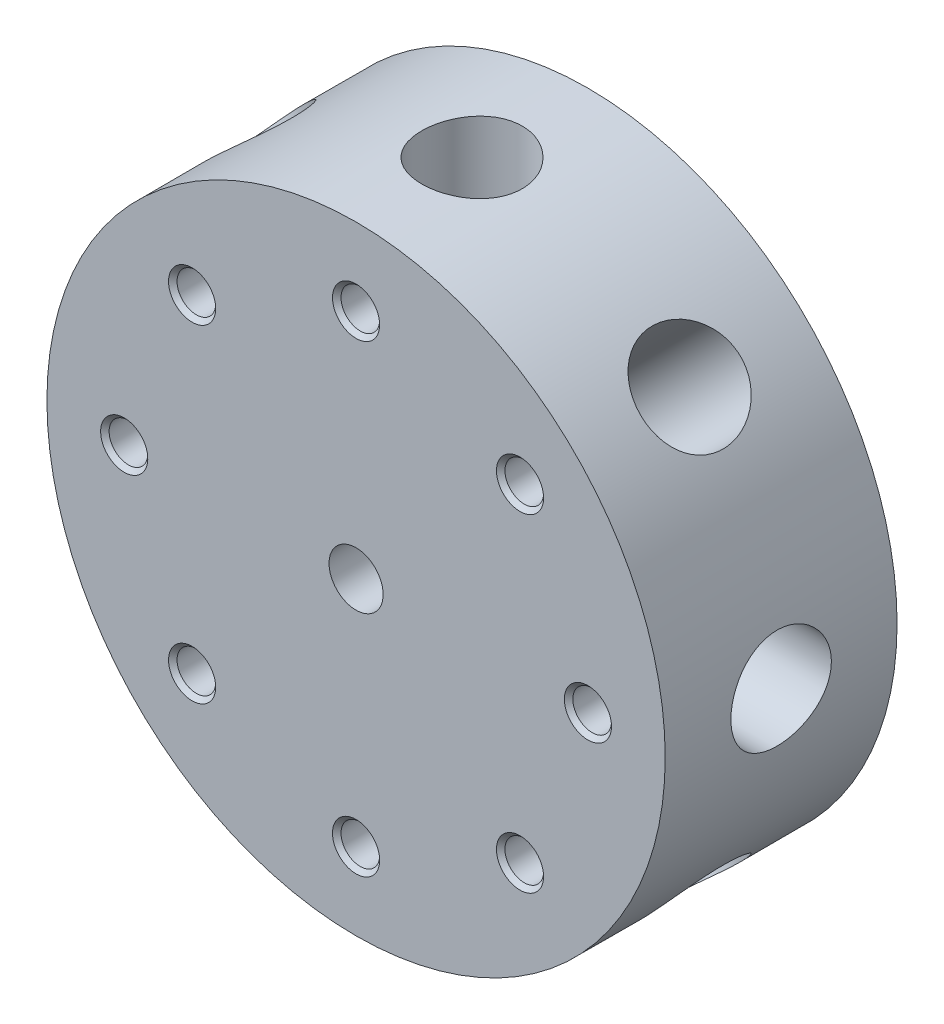
SolidWorks part; units mm, degrees
material "Nylon 101"
ref_plane "Front Plane" through (0, 0, 0) normal (0, 0, 1) x (1, 0, 0)
ref_plane "Top Plane" through (0, 0, 0) normal (0, 1, 0) x (1, 0, 0)
ref_plane "Right Plane" through (0, 0, 0) normal (1, 0, 0) x (0, 0, -1)
sketch "Sketch1" plane through (0, 0, 0) normal (0, 0, 1) x (1, 0, 0)
  circle A0 centre (0, 0) radius 40
  dimension "D1" = 80
extrude "Blank" add sketch "Sketch1" along normal mid plane 30
ref_plane "Plane1" through (0, 40, 0) normal (0, 1, 0) x (1, 0, 0)
hole_wizard "Ø12.0 stem hole" positions "Sketch7" profile "Sketch6" hole size "Ø12.0" standard "ANSI Metric"
sketch "Sketch7" plane through (0, 40, 0) normal (0, 1, 0) x (1, 0, 0)
  point P0 (0, 0)
sketch "Sketch6" plane through (0, 40, 0) normal (1, 0, 0) x (0, 0, 1)
  line L0 (0, 0) -> (0, 25.9056)
  line L1 (0, 25.9056) -> (6.5, 22)
  line L2 (6.5, 22) -> (6.5, 0)
  line L5 (6.5, 0) -> (0, 0)
  line L10 (0, 25.9056) -> (-6.5, 22) construction
  line L11 (0, -6.35) -> (0, 107.95) construction
  dimension "Hole Dia." = 13
  dimension "Hole Depth" = 22
  dimension "Drill Angle" = 118
hole_wizard "M6x1.0 Tapped Hole for grub screw" positions "Sketch4" profile "Sketch3" tap size "M6x1.0" standard "ANSI Metric" end condition up to next
sketch "Sketch4" plane through (0, 0, 15) normal (0, 0, 1) x (1, 0, 0)
  line L0 (0, 0) -> (0, 40) construction
  line L1 (16.5, 40) -> (-16.5, 40) construction
  circle A0 centre (0, 0) radius 40 construction
  point P0 (0, 30)
  dimension "D1" = 30
sketch "Sketch3" plane through (0, 30, 15) normal (1, 0, 0) x (0, -1, 0)
  line L0 (0, 0) -> (0, 8.5)
  line L1 (0, 8.5) -> (2.5, 8.5)
  line L2 (2.5, 8.5) -> (2.5, 0.55)
  line L3 (2.5, 0.55) -> (3.05, 0)
  line L5 (3.05, 0) -> (0, 0)
  line L6 (-2.5, 0.55) -> (-3.05, 0) construction
  line L11 (0, -6.35) -> (0, 107.95) construction
  dimension "Thru Tap Drill Dia." = 5
  dimension "Thru Tap Drill Depth" = 8.5
  dimension "Near C'Sink Dia." = 6.1
  dimension "Near C'Sink Angle" = 90
pattern_circular "CirPattern1" count 8 over 360 about axis through (0, 0, 15) along (0, 0, -1) of "M6x1.0 Tapped Hole for grub screw", "Ø12.0 stem hole"
sketch "Sketch5" plane through (0, 0, 15) normal (0, 0, 1) x (1, 0, 0)
  circle A0 centre (0, 0) radius 3.5
  dimension "D1" = 7
extrude "shaft_hole" cut sketch "Sketch5" against normal through all
